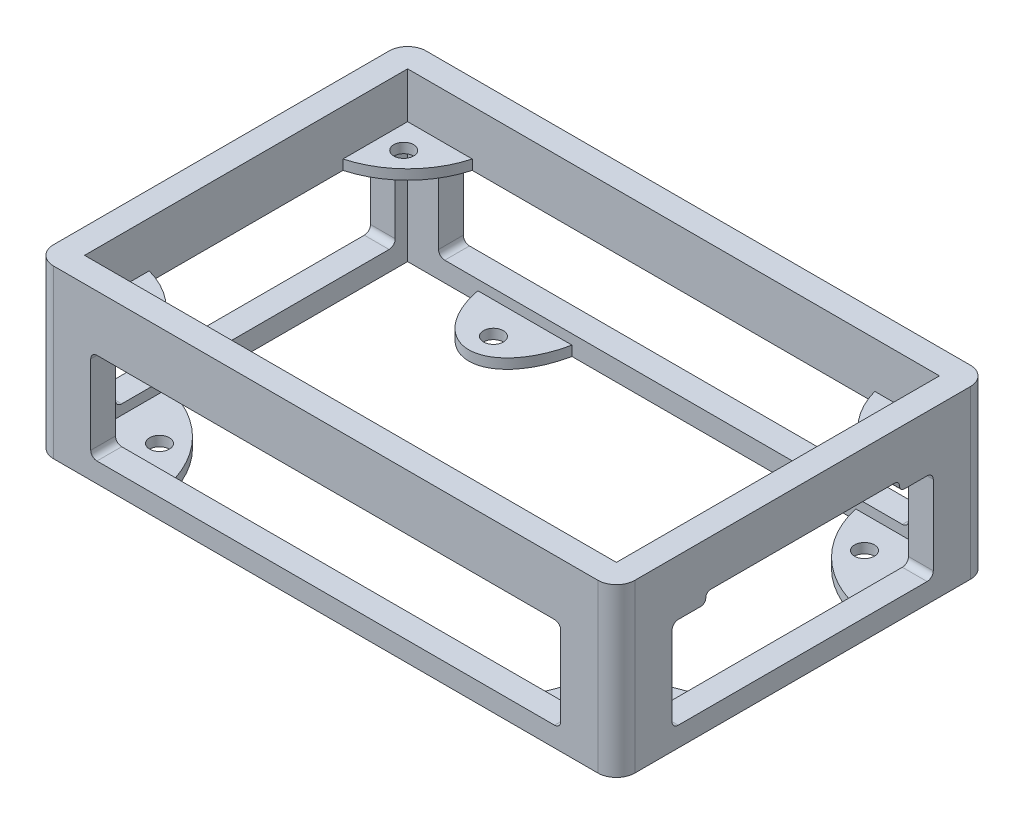
SolidWorks part; units mm, degrees
ref_plane "前视基准面" through (0, 0, 0) normal (0, 0, 1) x (1, 0, 0)
ref_plane "上视基准面" through (0, 0, 0) normal (0, 1, 0) x (1, 0, 0)
ref_plane "右视基准面" through (0, 0, 0) normal (1, 0, 0) x (0, 0, -1)
other "Configuration Table"
sketch "草图1" plane through (0, 0, 0) normal (0, 1, 0) x (1, 0, 0)
  line L0 (0, 0) -> (-65.3639, 0) construction
  line L1 (-43, 26.12) -> (-32.5432, 26.12)
  line L2 (-43, 26.12) -> (-43, -26.12)
  line L3 (-43, -26.12) -> (-32.5432, -26.12)
  line L4 (43, 26.12) -> (43, 15.6632)
  line L5 (-43, 26.12) -> (43, -26.12) construction
  line L6 (-43, -26.12) -> (43, 26.12) construction
  line L7 (0, 0) -> (0, 39.2677) construction
  line L8 (32.5432, 26.12) -> (43, 26.12)
  line L9 (-47, 30.12) -> (47, 30.12)
  line L10 (-47, 30.12) -> (-47, -30.12)
  line L11 (-47, -30.12) -> (47, -30.12)
  line L12 (47, 30.12) -> (47, -30.12)
  line L13 (-47, 30.12) -> (47, -30.12) construction
  line L14 (-47, -30.12) -> (47, 30.12) construction
  line L15 (43, -15.6632) -> (43, -26.12)
  line L16 (32.5432, -26.12) -> (43, -26.12)
  line L17 (-32.5432, 26.12) -> (32.5432, 26.12)
  line L18 (43, 15.6632) -> (43, -15.6632)
  line L19 (32.5432, -26.12) -> (-32.5432, -26.12)
  circle A0 centre (-39.3, 21.79) radius 1.6
  circle A1 centre (39.3, 21.79) radius 1.6
  circle A2 centre (-39.3, -21.79) radius 1.6
  circle A3 centre (39.3, -21.79) radius 1.6
  arc A4 (-43, 15.6632) -> (-32.5432, 26.12) centre (-47, 30.12) ccw
  arc A5 (32.5432, 26.12) -> (43, 15.6632) centre (47, 30.12) ccw
  arc A6 (43, -15.6632) -> (32.5432, -26.12) centre (47, -30.12) ccw
  arc A7 (-32.5432, -26.12) -> (-43, -15.6632) centre (-47, -30.12) ccw
  point P0 (0, 0)
  dimension "D3" = 3.2
  dimension "D4" = 3.2
  dimension "D5" = 3.2
  dimension "D6" = 3.2
  dimension "D7" = 78.6
  dimension "D8" = 43.58
  dimension "D10" = 78.6
  dimension "D11" = 0
  dimension "D12" = 39.3
  dimension "D13" = 21.79
  dimension "D16" = 30
  dimension "D17" = 30
  dimension "D18" = 30
  dimension "D19" = 30
  dimension "D20" = 0
  dimension "D1" = 86
  dimension "D2" = 52.24
  dimension "D9" = 43.58
  dimension "D14" = 94
  dimension "D15" = 60.24
extrude "凸台-拉伸1" add sketch "草图1" along normal blind 9 and the other way blind 18 contours L12 L9 L10 L11 L1 L4 L3 L2 region at (0, 0, -29.0035)
extrude "凸台-拉伸2" add sketch "草图1<3>" along normal blind 1.6 contours L2 A4 L1 A0 | L8 A5 L4 A1 | L15 A6 L16 A3 | L3 A7 L2 A2 region at (-37.7716, 0, -25.9721) region at (37.7716, 0, -25.9721) region at (-36.498, 0, 19.618) region at (42.8521, 0, 20.8916)
sketch "草图1<3>" plane through (0, 0, 0) normal (0, 1, 0) x (1, 0, 0) same geometry as "草图1"
ref_plane "基准面1" through (0, -18, 0) normal (0, -1, 0) x (-1, 0, 0)
sketch "草图2" plane through (0, -18, 0) normal (0, -1, 0) x (-1, 0, 0)
  line L0 (0, 0) -> (-78.5864, 0) construction
  line L1 (-43, 26.12) -> (-29.4501, 26.12)
  line L2 (-43, 26.12) -> (-43, 12.5701)
  line L3 (-43, -26.12) -> (-29.4501, -26.12)
  line L4 (43, -12.5701) -> (43, -26.12)
  line L5 (-43, 26.12) -> (43, -26.12) construction
  line L6 (-43, -26.12) -> (43, 26.12) construction
  line L7 (-47, 30.12) -> (47, 30.12)
  line L8 (-47, 30.12) -> (-47, -30.12)
  line L9 (-47, -30.12) -> (47, -30.12)
  line L10 (47, 30.12) -> (47, -30.12)
  line L11 (-47, 30.12) -> (47, -30.12) construction
  line L12 (-47, -30.12) -> (47, 30.12) construction
  line L13 (0, 0) -> (0, 38.7568) construction
  line L14 (24, 21) -> (24, 34.9764) construction
  line L15 (-43, -12.5701) -> (-43, -26.12)
  line L16 (29.4501, -26.12) -> (43, -26.12)
  line L17 (16.4166, 26.12) -> (31.642, 26.12)
  circle A0 centre (-36, 21) radius 1.6
  circle A1 centre (24, 21) radius 1.6
  circle A2 centre (36, -21) radius 1.6
  circle A3 centre (-36, -21) radius 1.6
  arc A4 (-43, 12.5701) -> (-29.4501, 26.12) centre (-47, 30.12) ccw
  arc A6 (43, -12.5701) -> (29.4501, -26.12) centre (47, -30.12) ccw
  arc A8 (-29.4501, -26.12) -> (-43, -12.5701) centre (-47, -30.12) ccw
  ellipse E0 centre (24, 30.12) end of major axis (23.8468, 43.1191) minor radius 8.0006 (16.4166, 26.12) -> (31.642, 26.12) ccw
  point P0 (0, 0)
  point P7 (0, 0)
  dimension "D1" = 3.2
  dimension "D2" = 3.2
  dimension "D3" = 3.2
  dimension "D4" = 3.2
  dimension "D5" = 60
  dimension "D6" = 42
  dimension "D7" = 72
  dimension "D8" = 42
  dimension "D9" = 0
  dimension "D10" = 36
  dimension "D11" = 21
  dimension "D12" = 36
  dimension "D13" = 0
  dimension "D14" = 36
  dimension "D15" = 36
  dimension "D16" = 13
  dimension "D17" = 8
extrude "凸台-拉伸3" add sketch "草图2" against normal blind 1.6 contours L2 A4 L1 A0 | L17 E0 A1 | L4 A6 L16 A2 | L3 A8 L15 A3 region at (37.7375, -18, -20.7311) region at (37.7375, -18, 20.7311) region at (-37.7375, -18, 20.7311) region at (-24.0293, -18, -25.9431)
fillet "圆角1" radius 3 4 edges at (47, -4.5, -30.12) (47, -4.5, 30.12) (-47, -4.5, 30.12) (-47, -4.5, -30.12)
ref_plane "基准面2" through (-47, 0, 0) normal (-1, 0, 0) x (0, 0, 1)
sketch "草图3" plane through (-47, 0, 0) normal (-1, 0, 0) x (0, 0, 1)
  line L0 (-27.12, -18) -> (27.12, -18) construction
  line L1 (-21.12, 0) -> (21.12, 0)
  line L2 (-21.12, 0) -> (-21.12, -14.8)
  line L3 (-21.12, -14.8) -> (21.12, -14.8)
  line L4 (21.12, 0) -> (21.12, -14.8)
  line L5 (-21.12, 0) -> (21.12, -14.8) construction
  line L6 (-21.12, -14.8) -> (21.12, 0) construction
  line L7 (0, 9) -> (0, -21.9617) construction
  line L8 (-27.12, 9) -> (27.12, 9) construction
  point P0 (0, -7.4)
  dimension "D1" = 42.24
  dimension "D2" = 14.8
  dimension "D3" = 3.2
  dimension "D4" = 21.12
extrude "切除-拉伸1" cut sketch "草图3" against normal blind 4
ref_plane "基准面3" through (47, 0, 0) normal (1, 0, 0) x (0, 0, -1)
sketch "草图4" plane through (47, 0, 0) normal (1, 0, 0) x (0, 0, -1)
  line L0 (27.12, -18) -> (-27.12, -18) construction
  line L1 (-21.12, 0) -> (21.12, 0)
  line L2 (-21.12, 0) -> (-21.12, -14.8)
  line L3 (-21.12, -14.8) -> (21.12, -14.8)
  line L4 (21.12, 0) -> (21.12, -14.8)
  line L5 (-21.12, 0) -> (21.12, -14.8) construction
  line L6 (-21.12, -14.8) -> (21.12, 0) construction
  line L7 (0, 9) -> (0, -28.0129) construction
  line L8 (27.12, 9) -> (-27.12, 9) construction
  point P0 (0, -7.4)
  dimension "D1" = 42.24
  dimension "D2" = 14.8
  dimension "D3" = 3.2
  dimension "D4" = 21.12
extrude "切除-拉伸2" cut sketch "草图4" against normal blind 4 contours L2 | L4 L1 L2 L3 region at (47, -7.4, 0)
ref_plane "基准面4" through (0, 0, 30.12) normal (0, 0, 1) x (1, 0, 0)
sketch "草图5" plane through (0, 0, 30.12) normal (0, 0, 1) x (1, 0, 0)
  line L0 (0, 9) -> (0, -22.3818) construction
  line L1 (-44, 9) -> (44, 9) construction
  line L2 (-44, -18) -> (44, -18) construction
  line L3 (-38, 0) -> (38, 0)
  line L4 (-38, 0) -> (-38, -14.8)
  line L5 (-38, -14.8) -> (38, -14.8)
  line L6 (38, 0) -> (38, -14.8)
  line L7 (-38, 0) -> (38, -14.8) construction
  line L8 (-38, -14.8) -> (38, 0) construction
  point P5 (0, -7.4)
  dimension "D1" = 76
  dimension "D2" = 14.8
  dimension "D3" = 3.2
extrude "切除-拉伸3" cut sketch "草图5" against normal blind 4
ref_plane "基准面5" through (0, 0, -30.12) normal (0, 0, -1) x (-1, 0, 0)
sketch "草图6" plane through (0, 0, -30.12) normal (0, 0, -1) x (-1, 0, 0)
  line L0 (0, 9) -> (0, -25.714) construction
  line L1 (44, 9) -> (-44, 9) construction
  line L2 (44, -18) -> (-44, -18) construction
  line L3 (-38, 0) -> (38, 0)
  line L4 (-38, 0) -> (-38, -14.8)
  line L5 (-38, -14.8) -> (38, -14.8)
  line L6 (38, 0) -> (38, -14.8)
  line L7 (-38, 0) -> (38, -14.8) construction
  line L8 (-38, -14.8) -> (38, 0) construction
  point P5 (0, -7.4)
  dimension "D1" = 76
  dimension "D2" = 14.8
  dimension "D3" = 3.2
extrude "切除-拉伸4" cut sketch "草图6" against normal blind 4
fillet "圆角2" radius 1 14 edges at (-38, -14.8, -28.12) (-38, 0, -28.12) (38, -14.8, -28.12) (38, 0, -28.12) (-45, -14.8, 21.12) (-45, 0, 21.12) (-38, -14.8, 28.12) (-38, 0, 28.12) (38, -14.8, 28.12) (38, 0, 28.12) (45, -14.8, -21.12) (45, 0, -21.12) (45, 0, 21.12) (45, -14.8, 21.12)
sketch "草图8" plane through (-47, 0, 0) normal (-1, 0, 0) x (0, 0, 1)
  line L1 (-21.12, -14.8) -> (-24.12, -14.8)
  line L2 (-21.12, -14.8) -> (-21.12, 0)
  line L3 (-21.12, 0) -> (-24.12, 0)
  line L4 (-24.12, -14.8) -> (-24.12, 0)
  dimension "D1" = 3
extrude "切除-拉伸5" cut sketch "草图8" against normal blind 4
fillet "圆角3" radius 1 2 edges at (-45, -14.8, -24.12) (-45, 0, -24.12)
sketch "草图9" plane through (47, 0, 0) normal (1, 0, 0) x (0, 0, -1)
  line L0 (-20.12, 0) -> (20.12, 0) construction
  line L1 (-15.6632, 1.6) -> (15.6632, 1.6)
  line L2 (-15.6632, 1.6) -> (-15.6632, 0)
  line L3 (-15.6632, 0) -> (15.6632, 0)
  line L4 (15.6632, 1.6) -> (15.6632, 0)
  line L5 (-15.6632, 1.6) -> (15.6632, 0) construction
  line L6 (-15.6632, 0) -> (15.6632, 1.6) construction
  line L7 (-15.6632, 1.6) -> (-15.6632, 0) construction
  line L8 (15.6632, 1.6) -> (15.6632, 0) construction
  point P0 (0, 0.8)
  dimension "D1" = 1.6
  dimension "D2" = 0
  dimension "D3" = 0
  dimension "D4" = 0
extrude "切除-拉伸6" cut sketch "草图9" against normal blind 4
fillet "圆角5" radius 0.8 4 edges at (45, 1.6, 15.6632) (45, 1.6, -15.6632) (45, 0, -15.6632) (45, 0, 15.6632)
